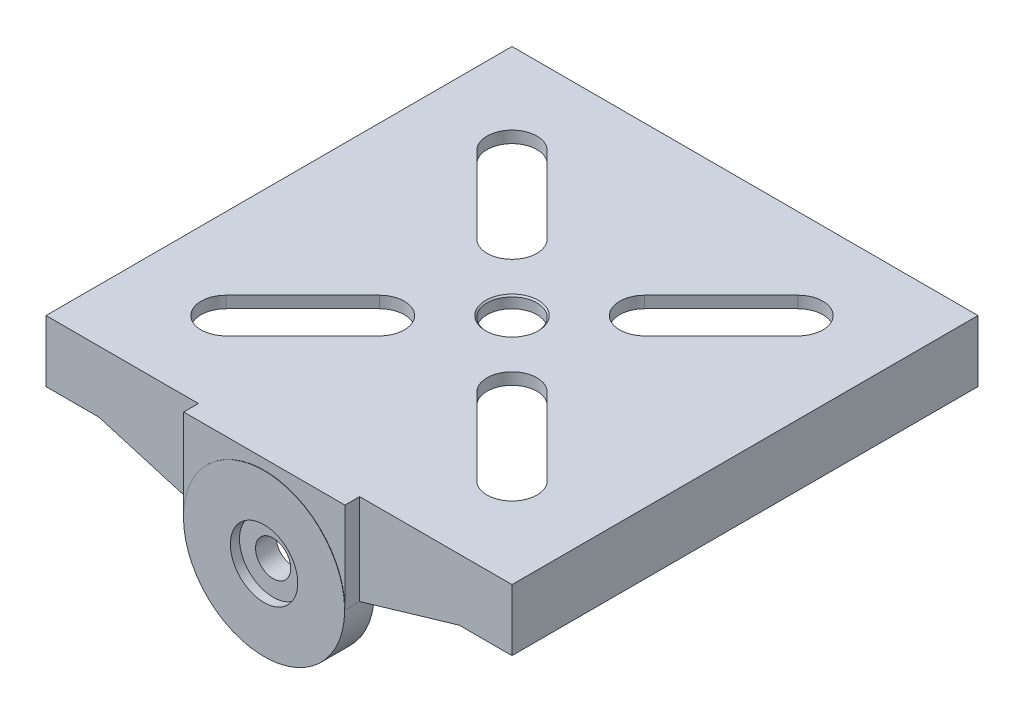
SolidWorks part; units mm, degrees
material "Gray Cast Iron"
ref_plane "Front Plane" through (0, 0, 0) normal (0, 0, 1) x (1, 0, 0)
ref_plane "Top Plane" through (0, 0, 0) normal (0, 1, 0) x (1, 0, 0)
ref_plane "Right Plane" through (0, 0, 0) normal (1, 0, 0) x (0, 0, -1)
sketch "Sketch2" plane through (0, 0, 0) normal (0, 1, 0) x (1, 0, 0)
  line L1 (0, 0) -> (159, 0)
  line L2 (0, 0) -> (0, 159)
  line L3 (0, 159) -> (159, 159)
  line L4 (159, 0) -> (159, 159)
  dimension "D1" = 159
  dimension "D2" = 159
extrude "Boss-Extrude1" add sketch "Sketch2" along normal blind 21
shell "Shell1" thickness 2 removed face at (79.5, 0, -79.5)
sketch "Sketch4" plane through (0, 0, 0) normal (0, 0, 1) x (1, 0, 0)
  line L0 (79.5, 21) -> (79.5, -10)
  line L1 (0, 21) -> (159, 21) construction
  line L2 (52, -10) -> (52, 21)
  line L3 (52, 21) -> (107, 21)
  line L4 (107, 21) -> (107, -10)
  circle A0 centre (79.5, -10) radius 27.5
  line M3 (0, 0) -> (159, 0)
  line M5 (159, 21) -> (0, 21)
  dimension "D2" = 55
  dimension "D1" = 31
extrude "Boss-Extrude2" add sketch "Sketch4" against normal blind 5 and the other way blind 5 contours A0 M3 | A0 L0 M3 | L0 A0 M3 | A0 L0 L2 M5 M3 | A0 L4 L0 M3 M5 | A0 L4 M3 | A0 L2 M3 region at (97.819, 14.707, 0) region at (61.181, 14.707, 0) region at (89.7038, 7.2348, 0) region at (69.2962, 7.2348, 0) region at (79.5, -16.4951, 0) region at (106.4387, -2.4826, 0) region at (52.5613, -2.4826, 0)
sketch "Sketch5" plane through (0, 0, 0) normal (0, 0, 1) x (1, 0, 0)
  line L0 (159, 0) -> (141, 0)
  line L1 (107, 0) -> (159, 0) construction
  line L2 (107, -10) -> (141, 0)
  line L3 (0, 0) -> (18, 0)
  line L4 (0, 0) -> (52, 0) construction
  line L5 (18, 0) -> (52, -10)
  line L6 (52, -10) -> (52, 0)
  line L7 (52, 0) -> (18, 0)
  line L8 (107, -10) -> (107, 0)
  line L9 (107, 0) -> (141, 0)
  line M5 (107, 0) -> (159, 0)
  dimension "D1" = 18
  dimension "D2" = 18
extrude "Boss-Extrude3" add sketch "Sketch5" against normal blind 2 contours L6 L7 L5 | L8 L2 M5 region at (118.3333, -3.3333, 0) region at (40.6667, -3.3333, 0)
sketch "Sketch6" plane through (0, 0, 5) normal (0, 0, 1) x (1, 0, 0)
  circle A0 centre (79.5, -10) radius 11.5
  dimension "D1" = 23
extrude "Cut-Extrude1" cut sketch "Sketch6" against normal blind 3
sketch "Sketch7" plane through (0, 0, 2) normal (0, 0, 1) x (1, 0, 0)
  circle A0 centre (79.5, -10) radius 6
  dimension "D1" = 12
extrude "Cut-Extrude2" cut sketch "Sketch7" against normal up to surface (7 mm away) up to face at (79.5, -2.375, -5)
sketch "Sketch8" plane through (0, 21, 0) normal (0, 1, 0) x (1, 0, 0)
  line L0 (79.5, 79.5) -> (56.8726, 102.1274)
  line L1 (79.5, 79.5) -> (102.1274, 102.1274)
  line L2 (79.5, 79.5) -> (102.1274, 56.8726)
  line L3 (79.5, 79.5) -> (56.8726, 56.8726)
  line L4 (56.8726, 56.8726) -> (30.7096, 30.7096)
  line L5 (56.8726, 102.1274) -> (30.7096, 128.2904)
  line L6 (102.1274, 102.1274) -> (128.2904, 128.2904)
  line L7 (102.1274, 56.8726) -> (128.2904, 30.7096)
  line L8 (24.6992, 122.28) -> (50.8622, 96.117)
  line L9 (36.72, 134.3008) -> (62.883, 108.1378)
  line L10 (122.28, 134.3008) -> (96.117, 108.1378)
  line L11 (134.3008, 122.28) -> (108.1378, 96.117)
  line L12 (96.117, 50.8622) -> (122.28, 24.6992)
  line L13 (108.1378, 62.883) -> (134.3008, 36.72)
  line L14 (62.883, 50.8622) -> (36.72, 24.6992)
  line L15 (50.8622, 62.883) -> (24.6992, 36.72)
  circle A0 centre (79.5, 79.5) radius 8.5
  circle A1 centre (56.8726, 56.8726) radius 8.5
  circle A2 centre (56.8726, 102.1274) radius 8.5
  circle A3 centre (102.1274, 102.1274) radius 8.5
  circle A4 centre (102.1274, 56.8726) radius 8.5
  circle A5 centre (30.7096, 30.7096) radius 8.5
  circle A6 centre (30.7096, 128.2904) radius 8.5
  circle A7 centre (128.2904, 128.2904) radius 8.5
  circle A8 centre (128.2904, 30.7096) radius 8.5
  dimension "D1" = 17
  dimension "D6" = 17
  dimension "D7" = 17
  dimension "D8" = 17
  dimension "D9" = 17
  dimension "D14" = 17
  dimension "D15" = 17
  dimension "D16" = 17
  dimension "D17" = 17
  dimension "D2" = 32
  dimension "D3" = 32
  dimension "D4" = 32
  dimension "D5" = 32
  dimension "D10" = 37
  dimension "D11" = 37
  dimension "D12" = 37
  dimension "D13" = 37
extrude "Cut-Extrude3" cut sketch "Sketch8" against normal through all contours A6 L5 A2 L9 | A6 L8 A2 L5 | A6 | L5 A2 L0 | L0 A2 L5 | L1 A0 L0 | L2 A0 L1 | L3 A0 L2 | L0 A0 L3 | L3 A1 L4 | A1 L3 L4 | A5 L14 A1 L4 | A5 L4 A1 L15 | A5 | L2 A4 L7 | L7 A4 L2 | A8 L7 A4 L12 | A8 L13 A4 L7 | A8 | A7 | A7 L6 A3 L11 | A7 L10 A3 L6 | L6 A3 L1 | A3 L6 L1 region at (74.3982, 21, -79.5) region at (79.5, 21, -84.6018) region at (84.6018, 21, -79.5) region at (79.5, 21, -74.3982) region at (54.3217, 21, -99.5765) region at (59.4235, 21, -104.6783) region at (99.5765, 21, -104.6783) region at (104.6783, 21, -99.5765) region at (104.6783, 21, -59.4235) region at (99.5765, 21, -54.3217) region at (59.4235, 21, -54.3217) region at (54.3217, 21, -59.4235) region at (40.5294, 21, -111.9472) region at (111.9472, 21, -118.4706) region at (118.4706, 21, -111.9472) region at (118.4706, 21, -47.0528) region at (111.9472, 21, -40.5294) region at (40.5294, 21, -47.0528) region at (47.0528, 21, -118.4706) region at (24.8692, 21, -134.1308) region at (131.4512, 21, -135.9212) region at (135.9212, 21, -33.8704) region at (47.0528, 21, -40.5294) region at (30.7096, 21, -38.9692)
sketch "Sketch9" plane through (0, 19, 0) normal (0, -1, 0) x (1, 0, 0)
  line L0 (79.5, -79.5) -> (56.8726, -56.8726) construction
  line L1 (77.0251, -81.9749) -> (54.3977, -59.3475)
  line L2 (81.9749, -77.0251) -> (59.3475, -54.3977)
  line L3 (79.5, -79.5) -> (102.1274, -56.8726) construction
  line L4 (77.0251, -77.0251) -> (99.6525, -54.3977)
  line L5 (81.9749, -81.9749) -> (104.6023, -59.3475)
  line L6 (79.5, -79.5) -> (56.8726, -102.1274) construction
  line L7 (81.9749, -81.9749) -> (59.3475, -104.6023)
  line L8 (77.0251, -77.0251) -> (54.3977, -99.6525)
  line L9 (79.5, -79.5) -> (102.1274, -102.1274) construction
  line L10 (81.9749, -77.0251) -> (104.6023, -99.6525)
  line L11 (77.0251, -81.9749) -> (99.6525, -104.6023)
  line L87 (64.6508, -49.0944) -> (38.4878, -22.9315)
  line L88 (22.9315, -38.4878) -> (49.0944, -64.6508)
  line L89 (64.6508, -49.0944) -> (38.4878, -22.9315)
  line L90 (22.9315, -38.4878) -> (49.0944, -64.6508)
  line L97 (109.9056, -64.6508) -> (136.0685, -38.4878)
  line L98 (120.5122, -22.9315) -> (94.3492, -49.0944)
  line L99 (109.9056, -64.6508) -> (136.0685, -38.4878)
  line L100 (120.5122, -22.9315) -> (94.3492, -49.0944)
  line L106 (38.4878, -136.0685) -> (64.6508, -109.9056)
  line L107 (49.0944, -94.3492) -> (22.9315, -120.5122)
  line L108 (38.4878, -136.0685) -> (64.6508, -109.9056)
  line L109 (49.0944, -94.3492) -> (22.9315, -120.5122)
  line L115 (136.0685, -120.5122) -> (109.9056, -94.3492)
  line L116 (94.3492, -109.9056) -> (120.5122, -136.0685)
  line L117 (136.0685, -120.5122) -> (109.9056, -94.3492)
  line L118 (94.3492, -109.9056) -> (120.5122, -136.0685)
  arc A0 (77.0251, -81.9749) -> (81.9749, -77.0251) centre (79.5, -79.5) ccw
  arc A1 (59.3475, -54.3977) -> (54.3977, -59.3475) centre (56.8726, -56.8726) ccw
  arc A2 (77.0251, -77.0251) -> (81.9749, -81.9749) centre (79.5, -79.5) ccw
  circle A3 centre (79.5, -79.5) radius 13.5
  circle A4 centre (79.5, -79.5) radius 13.5
  arc A5 (104.6023, -59.3475) -> (99.6525, -54.3977) centre (102.1274, -56.8726) ccw
  arc A6 (81.9749, -81.9749) -> (77.0251, -77.0251) centre (79.5, -79.5) ccw
  arc A7 (54.3977, -99.6525) -> (59.3475, -104.6023) centre (56.8726, -102.1274) ccw
  arc A8 (81.9749, -77.0251) -> (77.0251, -81.9749) centre (79.5, -79.5) ccw
  arc A9 (99.6525, -104.6023) -> (104.6023, -99.6525) centre (102.1274, -102.1274) ccw
  arc A83 (49.0944, -64.6508) -> (64.6508, -49.0944) centre (56.8726, -56.8726) ccw
  arc A84 (38.4878, -22.9315) -> (22.9315, -38.4878) centre (30.7096, -30.7096) ccw
  arc A85 (49.0944, -64.6508) -> (64.6508, -49.0944) centre (56.8726, -56.8726) ccw
  arc A86 (38.4878, -22.9315) -> (22.9315, -38.4878) centre (30.7096, -30.7096) ccw
  arc A91 (136.0685, -38.4878) -> (120.5122, -22.9315) centre (128.2904, -30.7096) ccw
  arc A92 (94.3492, -49.0944) -> (109.9056, -64.6508) centre (102.1274, -56.8726) ccw
  arc A93 (136.0685, -38.4878) -> (120.5122, -22.9315) centre (128.2904, -30.7096) ccw
  arc A94 (94.3492, -49.0944) -> (109.9056, -64.6508) centre (102.1274, -56.8726) ccw
  arc A100 (22.9315, -120.5122) -> (38.4878, -136.0685) centre (30.7096, -128.2904) ccw
  arc A101 (64.6508, -109.9056) -> (49.0944, -94.3492) centre (56.8726, -102.1274) ccw
  arc A102 (22.9315, -120.5122) -> (38.4878, -136.0685) centre (30.7096, -128.2904) ccw
  arc A103 (64.6508, -109.9056) -> (49.0944, -94.3492) centre (56.8726, -102.1274) ccw
  arc A109 (120.5122, -136.0685) -> (136.0685, -120.5122) centre (128.2904, -128.2904) ccw
  arc A110 (109.9056, -94.3492) -> (94.3492, -109.9056) centre (102.1274, -102.1274) ccw
  arc A111 (120.5122, -136.0685) -> (136.0685, -120.5122) centre (128.2904, -128.2904) ccw
  arc A112 (109.9056, -94.3492) -> (94.3492, -109.9056) centre (102.1274, -102.1274) ccw
  point P0 (68.1863, -68.1863)
  point P5 (90.8137, -68.1863)
  point P6 (65.7114, -70.6612)
  point P16 (68.1863, -90.8137)
  point P21 (90.8137, -90.8137)
  arc M18 (134.3008, -122.28) -> (122.28, -134.3008) centre (128.2904, -128.2904) cw
  line M19 (122.28, -134.3008) -> (96.117, -108.1378)
  arc M20 (96.117, -108.1378) -> (108.1378, -96.117) centre (102.1274, -102.1274) cw
  line M21 (108.1378, -96.117) -> (134.3008, -122.28)
  circle M22 centre (79.5, -79.5) radius 8.5
  line M23 (24.6992, -122.28) -> (50.8622, -96.117)
  arc M24 (50.8622, -96.117) -> (62.883, -108.1378) centre (56.8726, -102.1274) cw
  line M25 (62.883, -108.1378) -> (36.72, -134.3008)
  arc M26 (36.72, -134.3008) -> (24.6992, -122.28) centre (30.7096, -128.2904) cw
  arc M35 (24.6992, -36.72) -> (36.72, -24.6992) centre (30.7096, -30.7096) cw
  line M36 (36.72, -24.6992) -> (62.883, -50.8622)
  arc M37 (62.883, -50.8622) -> (50.8622, -62.883) centre (56.8726, -56.8726) cw
  line M38 (50.8622, -62.883) -> (24.6992, -36.72)
  arc M39 (122.28, -24.6992) -> (134.3008, -36.72) centre (128.2904, -30.7096) cw
  line M40 (134.3008, -36.72) -> (108.1378, -62.883)
  arc M41 (108.1378, -62.883) -> (96.117, -50.8622) centre (102.1274, -56.8726) cw
  line M42 (96.117, -50.8622) -> (122.28, -24.6992)
  dimension "D6" = 7
  dimension "D7" = 7
  dimension "D8" = 7
  dimension "D9" = 7
  dimension "D1" = 5
  dimension "D2" = 2.5
  dimension "D3" = 2.5
  dimension "D4" = 2.5
  dimension "D5" = 2.5
extrude "Boss-Extrude4" add sketch "Sketch9" along normal blind 2 contours L89 A86 L90 A85 L1 L2 M37 M38 M35 M36 | L117 A112 L10 L11 L118 A111 M20 M21 M18 M19 | L1 A85 L2 M37 | L10 A112 L11 M20 | L1 A4 L8 M22 | L2 A4 L1 M22 | L4 A4 L2 M22 | L5 A4 L4 M22 | L10 A4 L5 M22 | L11 A4 L10 M22 | L8 A4 L7 M22 | L7 A4 L11 M22 | A103 L7 A4 L8 | A112 L10 A4 L11 | A94 L4 A4 L5 | A85 L1 A4 L2 | L100 A94 L4 L5 L99 A93 M41 M42 M39 M40 | L108 A103 L7 L8 L109 A102 M24 M25 M26 M23 | L7 A103 L8 M24 | L4 A94 L5 M41 region at (68.5896, 19, -79.5) region at (71.8652, 19, -71.8652) region at (71.8652, 19, -87.1348) region at (79.5, 19, -90.4104) region at (87.1348, 19, -87.1348) region at (67.2893, 19, -67.2893) region at (79.5, 19, -68.5896) region at (67.2893, 19, -91.7107) region at (91.7107, 19, -91.7107) region at (90.4104, 19, -79.5) region at (87.1348, 19, -71.8652) region at (55.2092, 19, -67.0565) region at (63.6101, 19, -63.6101) region at (63.6101, 19, -95.3899) region at (60.3417, 19, -92.7453) region at (95.3899, 19, -95.3899) region at (92.7453, 19, -98.6583) region at (91.7107, 19, -67.2893) region at (95.3899, 19, -63.6101) region at (98.6583, 19, -66.2547)
ref_plane "Plane1" through (79.5, 0, 0) normal (1, 0, 0) x (0, 0, -1)
sketch "Sketch12" plane through (0, 0, -5) normal (0, 0, -1) x (-1, 0, 0)
  line L0 (-79.5, 19) -> (-79.5, 5.9321)
  line L1 (-107, 19) -> (-52, 19) construction
sketch "Sketch13" plane through (79.5, 0, 0) normal (1, 0, 0) x (0, 0, -1)
  line L0 (5, 19) -> (5, 3)
  line L1 (5, 19) -> (21, 19)
  line L2 (21, 19) -> (5, 3)
  dimension "D1" = 16
  dimension "D2" = 16
extrude "Boss-Extrude5" add sketch "Sketch13" against normal blind 2 from offset 27.5
extrude "Boss-Extrude6" add sketch "Sketch13<2>" along normal blind 2 from offset 27.5 offset against normal yes
sketch "Sketch13<2>" plane through (79.5, 0, 0) normal (1, 0, 0) x (0, 0, -1) same geometry as "Sketch13"
chamfer "Chamfer3" distance 0.5 angle 45 1 edges at (79.5, 21, -71)
sketch "Sketch14" plane through (0, 0, 5) normal (0, 0, 1) x (1, 0, 0)
  circle A0 centre (79.5, -10) radius 27.5
  circle A2 centre (79.5, -10) radius 11.5 construction
  circle A3 centre (79.5, -10) radius 11.5
extrude "Boss-Extrude7" add sketch "Sketch14" along normal blind 0.1
